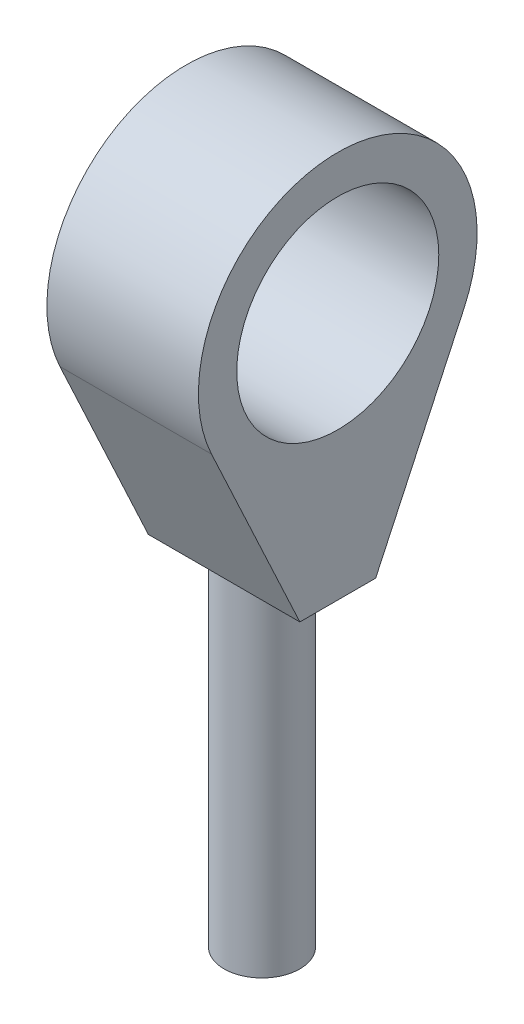
SolidWorks part; units mm, degrees
ref_plane "Front Plane" through (0, 0, 0) normal (0, 0, 1) x (1, 0, 0)
ref_plane "Top Plane" through (0, 0, 0) normal (0, 1, 0) x (1, 0, 0)
ref_plane "Right Plane" through (0, 0, 0) normal (1, 0, 0) x (0, 0, -1)
sketch "Sketch2" plane through (0, 0, 0) normal (0, 1, 0) x (1, 0, 0)
  circle A0 centre (0, 0) radius 4.7625
  dimension "D1" = 9.525
extrude "Boss-Extrude1" add sketch "Sketch2" along normal blind 42.545
sketch "Sketch3" plane through (0, 0, 0) normal (1, 0, 0) x (0, 0, -1)
  line L0 (-4.7625, 42.545) -> (-15.875, 66.3758)
  line L1 (4.7625, 42.545) -> (15.875, 66.3758)
  line L2 (-4.7625, 42.545) -> (-4.7625, 0) construction
  line L5 (-4.7625, 42.545) -> (4.7625, 42.545)
  arc A0 (-15.875, 66.3758) -> (15.875, 66.3758) centre (0, 73.7785) cw
  circle A1 centre (0, 73.7785) radius 12.7
  dimension "D3" = 25.4
  dimension "D1" = 155
  dimension "D2" = 31.75
extrude "Boss-Extrude2" add sketch "Sketch3" along normal blind 9.525 and the other way blind 9.525
